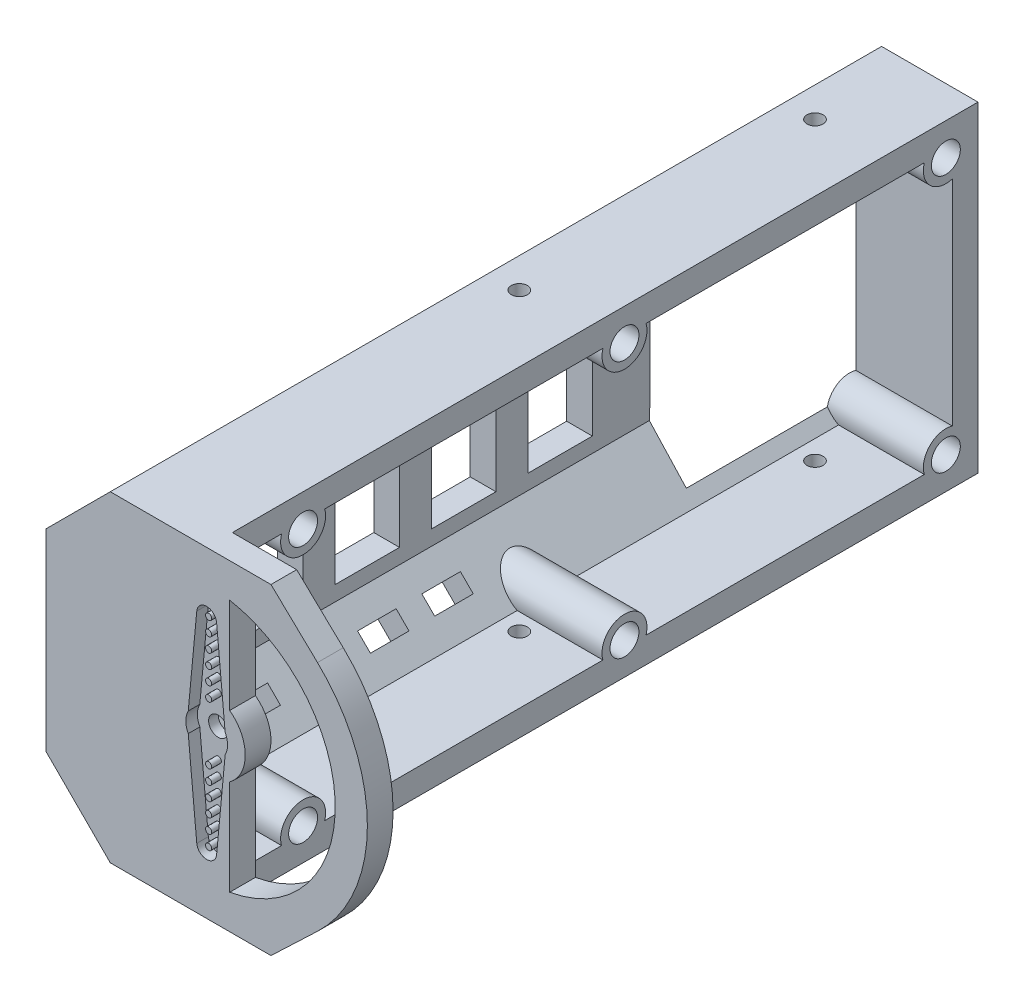
SolidWorks part; units mm, degrees
material "ABS"
ref_plane "Ön Düzlem" through (0, 0, 0) normal (0, 0, 1) x (1, 0, 0)
ref_plane "Üst Düzlem" through (0, 0, 0) normal (0, 1, 0) x (1, 0, 0)
ref_plane "Sağ Düzlem" through (0, 0, 0) normal (1, 0, 0) x (0, 0, -1)
sketch "Sketch2" plane through (0, 0, 0) normal (0, 0, 1) x (1, 0, 0)
  line L0 (0, -25) -> (-15, -25)
  line L1 (-25, -15) -> (-25, 15)
  line L2 (-15, 25) -> (0, 25)
  line L4 (-15, 25) -> (-25, 15)
  line L5 (-25, -15) -> (-15, -25)
  line L6 (0, -25) -> (10, -25)
  line L8 (10, 25) -> (0, 25)
  line L9 (10, 25) -> (17.2414, 18.1034)
  line L10 (10, -25) -> (17.2414, -18.1034)
  arc A0 (17.2414, -18.1034) -> (17.2414, 18.1034) centre (0, 0) ccw
  dimension "D1" = 50
  dimension "D2" = 10
  dimension "D4" = 15
  dimension "D3" = 10
  dimension "D5" = 10
extrude "Boss-Extrude1" add sketch "Sketch2" along normal blind 120
ref_plane "Plane1" through (0, -25, 0) normal (0, 1, 0) x (1, 0, 0)
sketch "Sketch3" plane through (0, -25, 0) normal (0, 1, 0) x (1, 0, 0)
  line L0 (25.8645, -116) -> (25.8645, 0.2893)
  line L4 (0, 0.2893) -> (25.8645, 0.2893)
  line L7 (25.8645, -116) -> (0, -116)
  line L8 (0, 0.2893) -> (0, -116)
  line L9 (17.2414, -120) -> (25, -120) construction
  dimension "D1" = 4
extrude "Cut-Extrude1" cut sketch "Sketch3" along normal up to next
shell "Shell1" thickness 4 removed face at (0, 0, 58)
sketch "Sketch5" plane through (0, 0, 120) normal (0, 0, 1) x (1, 0, 0)
  line L0 (0, 19.1079) -> (0, -19.1079) construction
  line L1 (-2.8699, -1.5252) -> (-1.5432, -15.645)
  line L2 (2.8699, -1.5252) -> (1.5432, -15.645)
  line L3 (-2.8699, -15.5) -> (3.4875, -15.5) construction
  line L4 (-5.1256, 0) -> (-3.25, 0) construction
  line L5 (-2.8699, 15.5) -> (3.4875, 15.5) construction
  line L6 (2.8699, 1.5252) -> (1.5432, 15.645)
  line L7 (-2.8699, 1.5252) -> (-1.5432, 15.645)
  line L8 (3.25, 0) -> (5.3089, 0) construction
  arc A0 (2.8699, -1.5252) -> (2.8699, 1.5252) centre (0, 0) ccw
  arc A2 (-1.5432, -15.645) -> (1.5432, -15.645) centre (0, -15.5) ccw
  arc A3 (-1.5432, 15.645) -> (1.5432, 15.645) centre (0, 15.5) cw
  arc A5 (-2.8699, 1.5252) -> (-2.8699, -1.5252) centre (0, 0) ccw
  dimension "D1" = 15.5
  dimension "D3" = 6.5
  dimension "D4" = 3.1
extrude "Cut-Extrude2" cut sketch "Sketch5" against normal blind 1.8
sketch "Sketch6" plane through (0, 0, 118.2) normal (0, 0, 1) x (1, 0, 0)
  circle A0 centre (0, 0) radius 1.5
  dimension "D1" = 3
extrude "Cut-Extrude3" cut sketch "Sketch6" against normal up to next contours A0
sketch "Sketch7" plane through (0, 0, 116) normal (0, 0, -1) x (-1, 0, 0)
  circle A0 centre (0, 0) radius 2.5
extrude "Cut-Extrude4" cut sketch "Sketch7" against normal offset from surface (0.7 mm away) 1.5 up to face at (1.5, 0, 118.2)
sketch "Sketch8" plane through (0, 0, 118.2) normal (0, 0, 1) x (1, 0, 0)
  line L0 (0, -19.5199) -> (0, 19.5199) construction
  line L1 (0, 0) -> (4.5827, 0) construction
  line L2 (0, 0) -> (-4.346, 0) construction
  circle A0 centre (0, 15.5) radius 0.48
  circle A1 centre (0, 13.3) radius 0.48
  circle A2 centre (0, 11.1) radius 0.48
  circle A3 centre (0, 8.9) radius 0.48
  circle A4 centre (0, 6.7) radius 0.48
  circle A5 centre (0, 4.5) radius 0.48
  circle A6 centre (0, -4.5) radius 0.48
  circle A7 centre (0, -6.7) radius 0.48
  circle A8 centre (0, -8.9) radius 0.48
  circle A9 centre (0, -11.1) radius 0.48
  circle A10 centre (0, -13.3) radius 0.48
  circle A11 centre (0, -15.5) radius 0.48
  dimension "D1" = 6
extrude "Boss-Extrude2" add sketch "Sketch8" along normal blind 1.5 contours A1 | A1 | A3 | A3 | A0 | A2 | A4 | A5 region at (0, 13.3, 118.2) region at (0, 8.9, 118.2)
extrude "Boss-Extrude3" add sketch "Sketch8<3>" along normal blind 1.5 contours A7 | A8 | A9 | A10 | A11 | A6 region at (0, -6.7, 118.2) region at (0, -8.9, 118.2) region at (0, -11.1, 118.2) region at (0, -13.3, 118.2) region at (0, -15.5, 118.2)
sketch "Sketch8<3>" plane through (0, 0, 118.2) normal (0, 0, 1) x (1, 0, 0) same geometry as "Sketch8"
sketch "Sketch9" plane through (0, 0, 120) normal (0, 0, 1) x (1, 0, 0)
  line L0 (3.5786, 19.6772) -> (3.5786, 4.816)
  line L1 (3.5786, -4.816) -> (3.5786, -19.6772)
  arc A0 (3.5786, -4.816) -> (3.5786, 4.816) centre (0, 0) ccw
  arc A1 (3.5786, -19.6772) -> (3.5786, 19.6772) centre (0, 0) ccw
extrude "Cut-Extrude5" cut sketch "Sketch9" against normal up to next
sketch "Sketch15" plane through (0, 0, 0) normal (1, 0, 0) x (0, 0, -1)
  line L0 (0, 25) -> (0, -25) construction
  line L1 (7.6061, 0) -> (-105.9288, 0) construction
  line L2 (-5, -21) -> (-5, -20)
  line L3 (-55, -30.5832) -> (-55, 30.3677) construction
  line L4 (0, -25) -> (-116, -25) construction
  line L5 (-116, 25) -> (0, 25) construction
  circle A0 centre (-5, -20) radius 3.5
  circle A1 centre (-5, 20) radius 3.5
  circle A2 centre (-105, 20) radius 3.5
  circle A3 centre (-105, -20) radius 3.5
  circle A4 centre (-55, -20) radius 3.5
  circle A5 centre (-55, 20) radius 3.5
  line M6 (-4, 21) -> (-4, -21)
  line M13 (-4, -21) -> (-116, -21)
  dimension "D1" = 20
  dimension "D2" = 5
  dimension "D3" = 7
  dimension "D5" = 5
  dimension "D6" = 5
  dimension "D4" = 50
extrude "Boss-Extrude6" add sketch "Sketch15" against normal up to surface (21 mm away) contours A3 M13 | A1 | A2 region at (0, -19.0379, 105) up to face at (-21, 0, 60)
sketch "Sketch16" plane through (0, 0, 0) normal (0, 0, -1) x (-1, 0, 0)
  line L0 (15, 25) -> (25, 15)
  line L1 (25, 15) -> (21.7476, 24.5697)
  line L2 (21.7476, 24.5697) -> (15, 25)
extrude "Cut-Extrude7" cut sketch "Sketch16" against normal up to surface (120 mm away) up to face at (8.2893, 0, 120)
extrude "Boss-Extrude8" add sketch "Sketch15<5>" against normal up to surface (14.3431 mm away) contours A5 up to face at (-16.9811, 17.3621, 65.6646)
sketch "Sketch15<5>" plane through (0, 0, 0) normal (1, 0, 0) x (0, 0, -1) same geometry as "Sketch15"
extrude "Boss-Extrude7" add sketch "Sketch15<4>" against normal up to surface (13.3431 mm away) contours A0 M6 M13 | A4 region at (0, -18.9708, 6.0292) up to face at (-16.6454, -17.6977, 75)
sketch "Sketch15<4>" plane through (0, 0, 0) normal (1, 0, 0) x (0, 0, -1) same geometry as "Sketch15"
sketch "Sketch17" plane through (0, 0, 0) normal (0, 0, -1) x (-1, 0, 0)
  line L0 (15, -25) -> (25, -15)
  line L1 (25, -15) -> (23.6229, -22.657)
  line L2 (23.6229, -22.657) -> (15, -25)
extrude "Cut-Extrude8" cut sketch "Sketch17" against normal up to surface (120 mm away) up to face at (8.2893, 0, 120)
sketch "Sketch18" plane through (0, 0, 0) normal (1, 0, 0) x (0, 0, -1)
  line L0 (-55, 34.8702) -> (-55, -34.6602) construction
  line L1 (9.9372, 0) -> (-108.4776, 0) construction
  circle A0 centre (-5, 20) radius 2.25
  circle A1 centre (-5, -20) radius 2.25
  circle A2 centre (-105, 20) radius 2.25
  circle A3 centre (-105, -20) radius 2.25
  circle A4 centre (-55, -20) radius 2.25
  circle A5 centre (-55, 20) radius 2.25
  dimension "D1" = 50
  dimension "D2" = 4.5
  dimension "D3" = 4.5
extrude "Cut-Extrude9" cut sketch "Sketch18" against normal blind 15
sketch "Sketch22" plane through (0, -21, 0) normal (0, 1, 0) x (1, 0, 0)
  line L1 (-13.3431, -7.0156) -> (0, -7.0156) construction
  line L2 (-13.3431, -101.6459) -> (-13.3431, -58.3541) construction
  circle A0 centre (-10.3431, -15.0156) radius 1.25
  circle A1 centre (-10.3431, -61.0156) radius 1.25
  dimension "D1" = 2.5
  dimension "D2" = 8
  dimension "D4" = 46
  dimension "D5" = 2.5
  dimension "D6" = 3
  dimension "D3" = 3
extrude "Cut-Extrude10" cut sketch "Sketch22" against normal up to next contours A1 | A0
ref_plane "Plane5" through (0, 0, 0) normal (0, -1, 0) x (-1, 0, 0)
mirror "Mirror1" about plane through (0, 0, 0) normal (0, -1, 0) of "Cut-Extrude10"
sketch "Sketch23" plane through (-21, 0, 0) normal (1, 0, 0) x (0, 0, -1)
  line L0 (-13.75, 0) -> (13.75, 0) construction
  line L1 (-49, -11) -> (-39, -11)
  line L2 (-49, -11) -> (-49, 11)
  line L3 (-49, 11) -> (-39, 11)
  line L4 (-39, -11) -> (-39, 11)
  line L5 (-49, -11) -> (-39, 11) construction
  line L6 (-49, 11) -> (-39, -11) construction
  line L8 (-64, -11) -> (-64, 11)
  line L9 (-64, -11) -> (-54, -11)
  line L10 (-54, -11) -> (-54, 11)
  line L11 (-64, 11) -> (-54, 11)
  line L12 (-79, -11) -> (-79, 11)
  line L13 (-79, -11) -> (-69, -11)
  line L14 (-69, -11) -> (-69, 11)
  line L15 (-79, 11) -> (-69, 11)
  line L16 (-94, -11) -> (-94, 11)
  line L17 (-94, -11) -> (-84, -11)
  line L18 (-84, -11) -> (-84, 11)
  line L19 (-94, 11) -> (-84, 11)
  line L20 (-109, -11) -> (-109, 11)
  line L21 (-109, -11) -> (-99, -11)
  line L22 (-99, -11) -> (-99, 11)
  line L23 (-109, 11) -> (-99, 11)
  line L24 (-4, 13.3431) -> (-4, -13.3431) construction
  point P0 (-44, 0)
  dimension "D1" = 22
  dimension "D2" = 10
  dimension "D3" = 35
  dimension "D4" = 5
extrude "Cut-Extrude11" cut sketch "Sketch23" against normal up to surface (4 mm away) up to face at (-25, 0, 60)
sketch "Sketch25" plane through (-17.1716, 17.1716, 0) normal (0.7071, -0.7071, 0) x (0, 0, -1)
  line L0 (-51.6459, 5.4142) -> (-8.3541, 5.4142) construction
  line L2 (-12, 1.4142) -> (-18, 1.4142)
  line L3 (-18, 1.4142) -> (-18, -1.4158)
  line L4 (-18, -1.4158) -> (-12, -1.4158)
  line L5 (-12, -1.4158) -> (-12, 1.4142)
  line L8 (-4, -0.7434) -> (-4, -5.4142) construction
  line L9 (-22, 1.4142) -> (-28, 1.4142)
  line L10 (-28, 1.4142) -> (-28, -1.4158)
  line L11 (-28, -1.4158) -> (-22, -1.4158)
  line L12 (-22, -1.4158) -> (-22, 1.4142)
  line L13 (-32, 1.4142) -> (-38, 1.4142)
  line L14 (-38, 1.4142) -> (-38, -1.4158)
  line L15 (-38, -1.4158) -> (-32, -1.4158)
  line L16 (-32, -1.4158) -> (-32, 1.4142)
  line L17 (-42, 1.4142) -> (-48, 1.4142)
  line L18 (-48, 1.4142) -> (-48, -1.4158)
  line L19 (-48, -1.4158) -> (-42, -1.4158)
  line L20 (-42, -1.4158) -> (-42, 1.4142)
  line L21 (-55, -0.9497) -> (-55, -4.8783)
  line L22 (-92, 1.4142) -> (-92, -1.4158)
  line L23 (-98, -1.4158) -> (-98, 1.4142)
  line L24 (-98, 1.4142) -> (-92, 1.4142)
  line L25 (-68, -1.4158) -> (-68, 1.4142)
  line L26 (-62, -1.4158) -> (-68, -1.4158)
  line L27 (-62, 1.4142) -> (-62, -1.4158)
  line L28 (-68, 1.4142) -> (-62, 1.4142)
  line L29 (-78, -1.4158) -> (-78, 1.4142)
  line L30 (-72, -1.4158) -> (-78, -1.4158)
  line L31 (-72, 1.4142) -> (-72, -1.4158)
  line L32 (-78, 1.4142) -> (-72, 1.4142)
  line L33 (-88, -1.4158) -> (-88, 1.4142)
  line L34 (-82, -1.4158) -> (-88, -1.4158)
  line L35 (-82, 1.4142) -> (-82, -1.4158)
  line L36 (-88, 1.4142) -> (-82, 1.4142)
  line L37 (-92, -1.4158) -> (-98, -1.4158)
  ellipse E0 centre (-55, 4) end of major axis (-55, 8.9497) minor radius 3.5 (-58.3541, 5.4142) -> (-51.6459, 5.4142) ccw construction
  dimension "D1" = 2.83
  dimension "D2" = 4
  dimension "D3" = 6
  dimension "D4" = 8
  dimension "D5" = 4
extrude "Cut-Extrude13" cut sketch "Sketch25" against normal up to next contours L4 L5 L2 L3 | L11 L12 L9 L10 | L15 L16 L13 L14 | L19 L20 L17 L18 | L28 L25 L26 L27 | L37 L22 L24 L23 | L36 L33 L34 L35 | L32 L29 L30 L31 region at (-17.1721, 17.171, 15) region at (-17.1721, 17.171, 25) region at (-17.1721, 17.171, 35) region at (-17.1721, 17.171, 45) region at (-17.1721, 17.171, 95) region at (-17.1721, 17.171, 65) region at (-17.1721, 17.171, 75) region at (-17.1721, 17.171, 85)
sketch "Sketch26" plane through (-17.1716, -17.1716, 0) normal (0.7071, 0.7071, 0) x (0, 0, -1)
  line L1 (-101.6459, -5.4142) -> (-58.3541, -5.4142) construction
  line L2 (-72.3541, -1.4142) -> (-72.3541, 1.4158)
  line L3 (-62.3541, -1.4142) -> (-62.3541, 1.4158)
  line L4 (-62.3541, 1.4158) -> (-68.3541, 1.4158)
  line L5 (-68.3541, 1.4158) -> (-68.3541, -1.4142)
  line L6 (-68.3541, -1.4142) -> (-62.3541, -1.4142)
  line L7 (-72.3541, 1.4158) -> (-78.3541, 1.4158)
  line L8 (-78.3541, 1.4158) -> (-78.3541, -1.4142)
  line L9 (-78.3541, -1.4142) -> (-72.3541, -1.4142)
  line L10 (-82.3541, -1.4142) -> (-82.3541, 1.4158)
  line L11 (-82.3541, 1.4158) -> (-88.3541, 1.4158)
  line L12 (-88.3541, 1.4158) -> (-88.3541, -1.4142)
  line L13 (-88.3541, -1.4142) -> (-82.3541, -1.4142)
  line L14 (-92.3541, -1.4142) -> (-92.3541, 1.4158)
  line L15 (-92.3541, 1.4158) -> (-98.3541, 1.4158)
  line L16 (-98.3541, 1.4158) -> (-98.3541, -1.4142)
  line L17 (-98.3541, -1.4142) -> (-92.3541, -1.4142)
  dimension "D1" = 2.83
  dimension "D2" = 6
  dimension "D3" = 4
  dimension "D4" = 4
  dimension "D5" = 4
extrude "Cut-Extrude14" cut sketch "Sketch26" against normal up to next
sketch "Sketch27" plane through (-25, 0, 0) normal (-1, 0, 0) x (0, 0, 1)
  line L1 (0, 25) -> (30, 25.3734)
  line L8 (0, 25) -> (0, -25)
  line L9 (30, 10) -> (30, 23.8624)
  line L12 (30, 10) -> (30, -10)
  line L16 (30, 25.3734) -> (30, 23.8624)
  line L17 (30, -10) -> (30.6373, -25.8286)
  line L18 (30.6373, -25.8286) -> (0, -25.8286)
  line L19 (0, -25.8286) -> (0, -25)
extrude "Cut-Extrude15" cut sketch "Sketch27" against normal up to vertex (10 mm away) up to point (-15, -25, 0)
